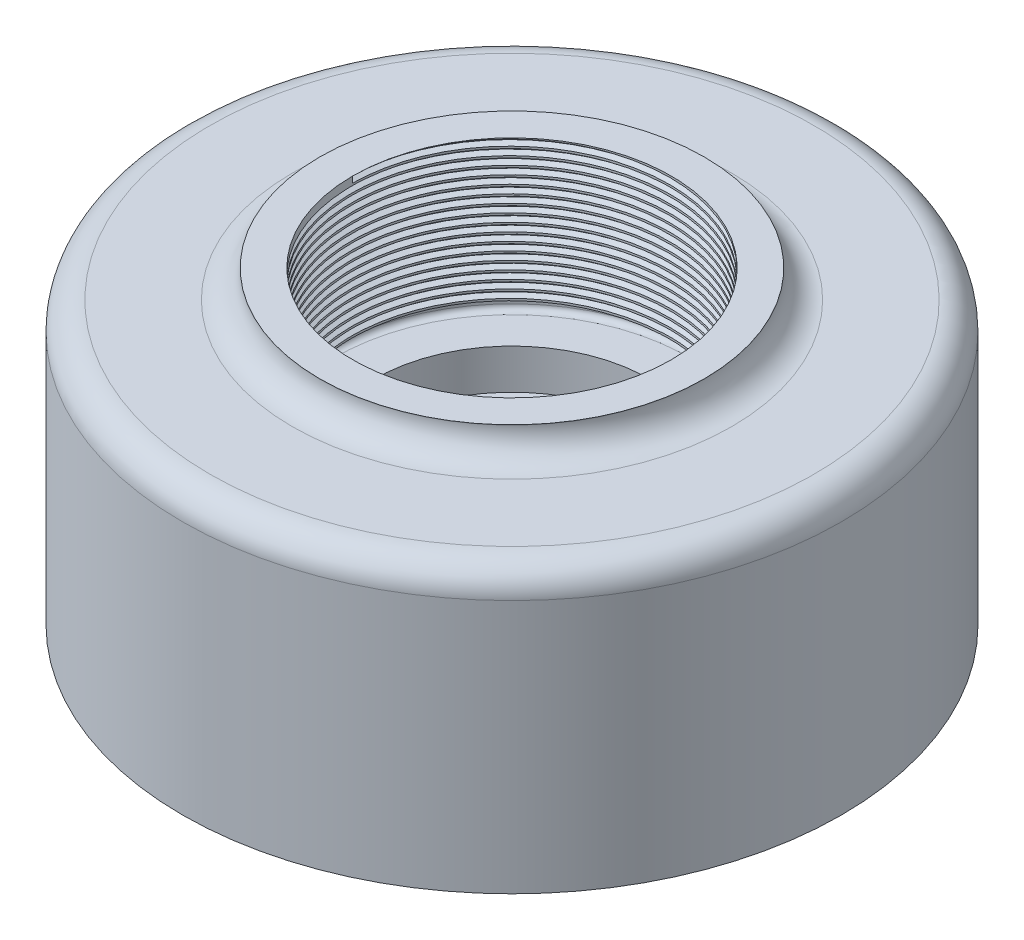
SolidWorks part; units mm, degrees
ref_plane "Front Plane" through (0, 0, 0) normal (0, 0, 1) x (1, 0, 0)
ref_plane "Top Plane" through (0, 0, 0) normal (0, 1, 0) x (1, 0, 0)
ref_plane "Right Plane" through (0, 0, 0) normal (1, 0, 0) x (0, 0, -1)
sketch "Sketch2" plane through (0, 0, 0) normal (0, 0, 1) x (1, 0, 0)
  line L0 (0, 81.9027) -> (0, -77.9204) construction
  line L1 (0, -15.7965) -> (-60, -15.7965)
  line L2 (-29, 40.4867) -> (-35, 40.4867)
  line L3 (-35, 40.4867) -> (-35, 40.4425)
  line L4 (-40, 35.4425) -> (-55, 35.4425)
  line L5 (-60, 30.4425) -> (-60, -15.7965)
  line L6 (-29, 14.4867) -> (-32, 14.4867)
  line L7 (-29, 40.4867) -> (-29, 14.4867)
  line L8 (-33, 13.4867) -> (-33, 11.4867)
  line L9 (-32, 10.4867) -> (-29, 10.4867)
  line L10 (-29, 10.4867) -> (-25, 10.4867)
  line L11 (-25, 10.4867) -> (-25, 3.2035)
  line L12 (-25, 3.2035) -> (0, 3.2035)
  line L13 (0, 3.2035) -> (0, -15.7965)
  arc A0 (-35, 40.4425) -> (-40, 35.4425) centre (-40, 40.4425) cw
  arc A1 (-55, 35.4425) -> (-60, 30.4425) centre (-55, 30.4425) ccw
  arc A2 (-33, 11.4867) -> (-32, 10.4867) centre (-32, 11.4867) ccw
  arc A3 (-32, 14.4867) -> (-33, 13.4867) centre (-32, 13.4867) ccw
  dimension "D3" = 5
  dimension "D4" = 5
  dimension "D7" = 1
  dimension "D1" = 120
  dimension "D2" = 70
  dimension "D5" = 58
  dimension "D6" = 26
  dimension "D8" = 50
  dimension "D9" = 19
revolve "Revolve1" add sketch "Sketch2" angle 360 about L0
thread "Thread1" pitch 1.5 method cut profile "Thread Profile1" start angle 0, offset 0, length 0, pitch 1.5, diameter 58
ref_plane "Plane1" through (-29, 40.4867, 0) normal (0, 0, 1) x (-1, 0, 0)
sketch "Thread Profile1" plane through (-29, 40.4867, 0) normal (0, 0, 1) x (-1, 0, 0)
  line L0 (0, 0) -> (0, 1.5) construction
  line L1 (0, 0) -> (0.8119, 0.4687)
  line L2 (0.8119, 0.4687) -> (0.8119, 0.6562)
  line L3 (0.8119, 0.6562) -> (0, 1.125)
  line L4 (0.8119, 0.5625) -> (0, 0.5625) construction
  line L11 (0, 0) -> (0, 1.125)
  point P2 (0, 0)
  dimension "Pitch" = 1.5
  dimension "Profile_Angle" = 60
  dimension "Profile_Land" = 0.1875
  dimension "Profile_Height" = 0.8119
